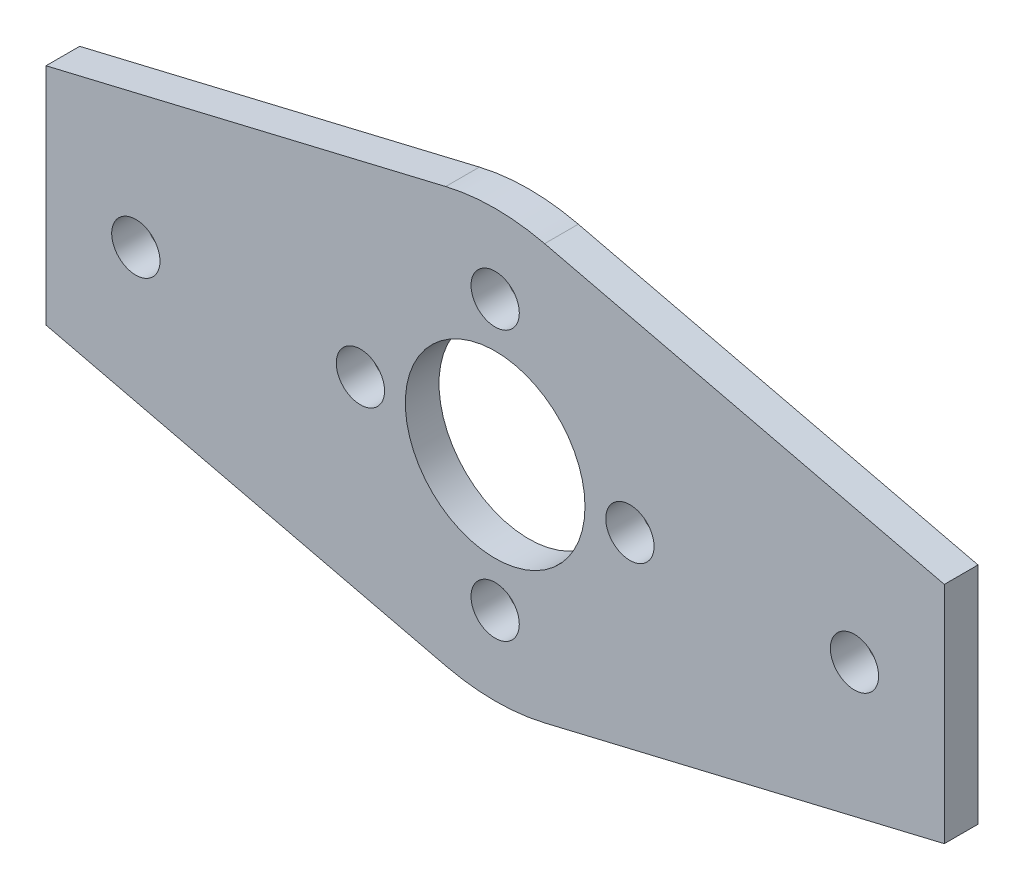
SolidWorks part; units mm, degrees
material "Thornel Mat VMA"
ref_plane "Front Plane" through (0, 0, 0) normal (0, 0, 1) x (1, 0, 0)
ref_plane "Top Plane" through (0, 0, 0) normal (0, 1, 0) x (1, 0, 0)
ref_plane "Right Plane" through (0, 0, 0) normal (1, 0, 0) x (0, 0, -1)
sketch "Sketch1" plane through (0, 0, 0) normal (0, 0, 1) x (1, 0, 0)
  line L0 (-65.3658, -264.7418) -> (-65.3658, -284.7418)
  line L1 (-380.3658, -264.7418) -> (329.6342, -264.7418) construction
  line L2 (-400.3658, -284.7418) -> (349.6342, -284.7418) construction
  line L3 (-65.3658, -264.7418) -> (-29.7702, -256.2594)
  line L4 (-65.3658, -284.7418) -> (-29.7702, -293.2243)
  line L5 (-25.3658, -255.7418) -> (-25.3658, -293.7418) construction
  line L6 (14.6342, -284.7418) -> (-20.9614, -293.2243)
  line L7 (14.6342, -264.7418) -> (-20.9614, -256.2594)
  line L8 (14.6342, -264.7418) -> (14.6342, -284.7418)
  line L9 (14.6342, -284.7418) -> (-20.9614, -293.2243)
  line L10 (14.6342, -264.7418) -> (14.6342, -284.7418)
  line L11 (14.6342, -264.7418) -> (-20.9614, -256.2594)
  line L12 (-65.3658, -264.7418) -> (-29.7702, -256.2594)
  line L13 (-65.3658, -264.7418) -> (-65.3658, -284.7418)
  line L14 (-65.3658, -284.7418) -> (-29.7702, -293.2243)
  arc A0 (-29.7702, -293.2243) -> (-20.9614, -293.2243) centre (-25.3658, -274.7418) ccw
  circle A1 centre (-57.3658, -274.7418) radius 2.15
  circle A2 centre (-37.3658, -274.7418) radius 2.15
  arc A3 (-20.9614, -256.2594) -> (-29.7702, -256.2594) centre (-25.3658, -274.7418) ccw
  circle A4 centre (-13.3658, -274.7418) radius 2.15
  circle A5 centre (6.6342, -274.7418) radius 2.15
  circle A6 centre (-25.3658, -274.7418) radius 8 construction
  circle A7 centre (-25.3658, -274.7418) radius 8
  circle A8 centre (-25.3658, -262.7418) radius 2.15
  circle A9 centre (-25.3658, -286.7418) radius 2.15
  dimension "D1" = 38
  dimension "D3" = 12
  dimension "D4" = 4.3
  dimension "D5" = 8
  dimension "D6" = 4.3
  dimension "D7" = 12
  dimension "D2" = 40
  dimension "D8" = 12
extrude "Extrude1" add sketch "Sketch1" along normal blind 3 contours L5 A3 L3 L0 L4 A0 A7 A1 A2 | A3 L5 A7 A0 L6 L8 L7 A5 A4 region at (-47.3627, -261.3621, 0)
